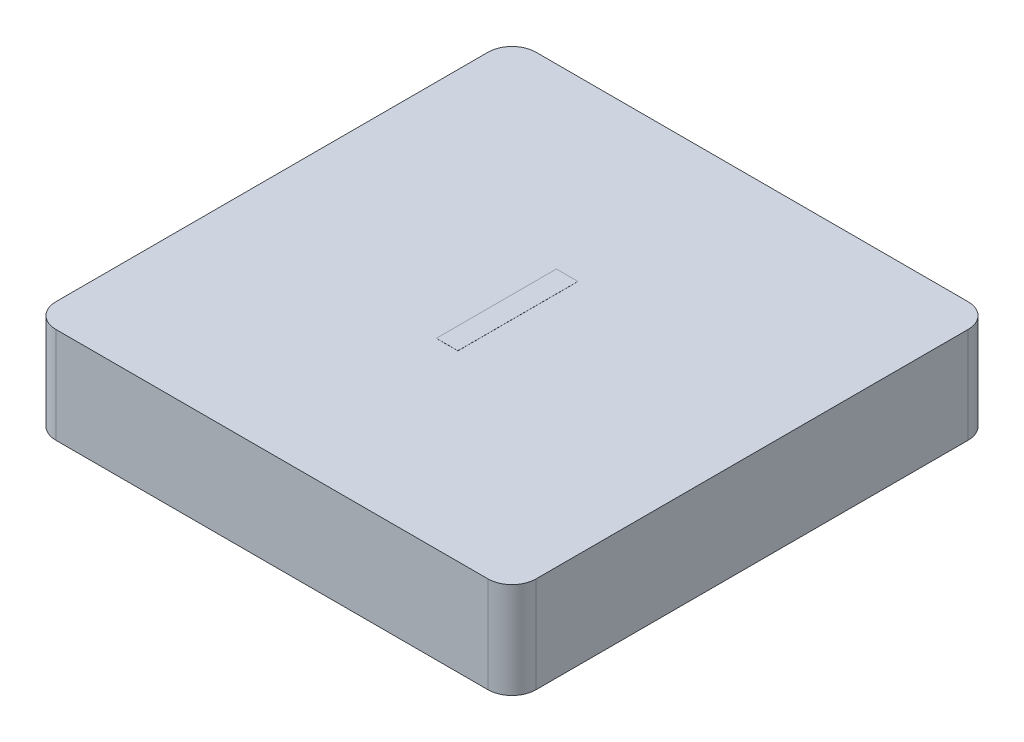
SolidWorks part; units mm, degrees
ref_plane "Front Plane" through (0, 0, 0) normal (0, 0, 1) x (1, 0, 0)
ref_plane "Top Plane" through (0, 0, 0) normal (0, 1, 0) x (1, 0, 0)
ref_plane "Right Plane" through (0, 0, 0) normal (1, 0, 0) x (0, 0, -1)
sketch "Sketch1" plane through (0, 0, 0) normal (0, 1, 0) x (1, 0, 0)
  line L0 (0, 0) -> (12.7, 0)
  line L1 (12.7, 0) -> (12.7, 12.7)
  line L2 (12.7, 12.7) -> (0, 12.7)
  line L3 (0, 12.7) -> (0, 0)
  dimension "D1" = 12.7
  dimension "D2" = 12.7
extrude "Boss-Extrude1" add sketch "Sketch1" along normal blind 2.54
fillet "Fillet1" radius 0.635 4 edges at (0, 1.27, -12.7) (12.7, 1.27, -12.7) (12.7, 1.27, 0) (0, 1.27, 0)
shell "Shell1" thickness 0.635 removed face at (6.35, 0, -6.35)
sketch "Sketch2" plane through (0, 1.905, 0) normal (0, -1, 0) x (-1, 0, 0)
  line L0 (-0.635, 6.35) -> (-12.065, 6.35) construction
  line L1 (-0.635, 12.065) -> (-0.635, 0.635) construction
  line L2 (-12.065, 0.635) -> (-12.065, 12.065) construction
  line L3 (-6.35, 0.635) -> (-6.35, 12.065) construction
  line L4 (-0.635, 0.635) -> (-12.065, 0.635) construction
  line L5 (-12.065, 12.065) -> (-0.635, 12.065) construction
  circle A0 centre (-6.35, 6.35) radius 2.54
  dimension "D1" = 5.08
extrude "Boss-Extrude2" add sketch "Sketch2" along normal up to surface (1.905 mm away) up to face at (6.35, 0, -6.35)
sketch "Sketch3" plane through (0, 2.54, 0) normal (0, 1, 0) x (1, 0, 0)
  line L0 (0, 12.065) -> (0, 0.635) construction
  line L1 (0.635, 0) -> (12.065, 0) construction
  text T0 "<b>I</b>"
  point P1 (0, 0)
  dimension "D1" = 5.588
  dimension "D2" = 4.826
extrude "Boss-Extrude3" add sketch "Sketch3" along normal blind 0.0025
